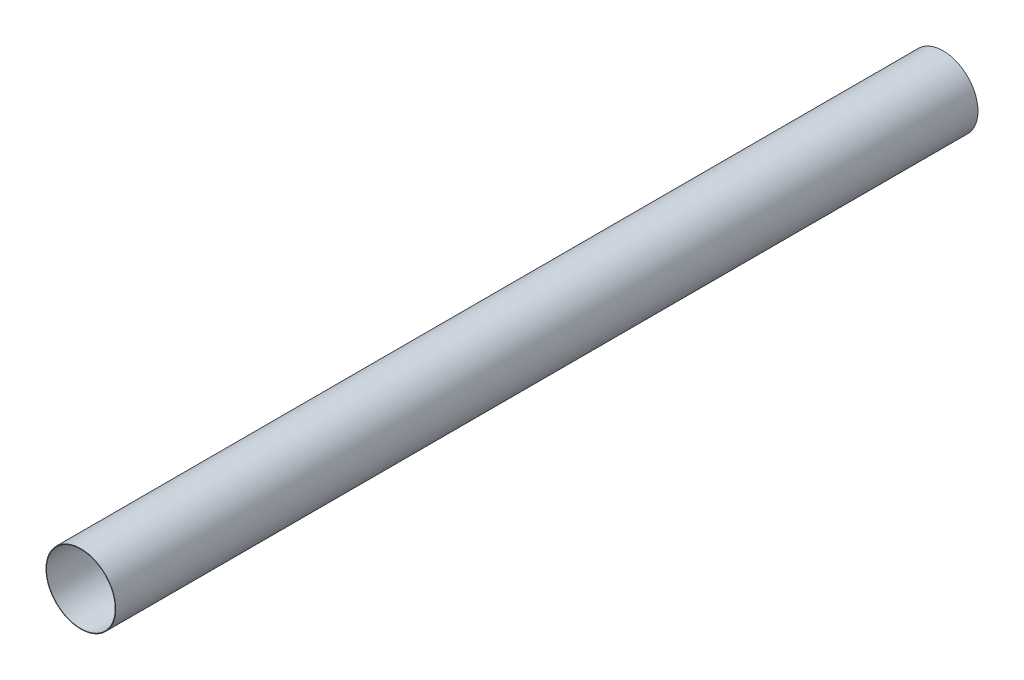
SolidWorks part; units mm, degrees
material "6061-T6 (SS)"
ref_plane "Front Plane" through (0, 0, 0) normal (0, 0, 1) x (1, 0, 0)
ref_plane "Top Plane" through (0, 0, 0) normal (0, 1, 0) x (1, 0, 0)
ref_plane "Right Plane" through (0, 0, 0) normal (1, 0, 0) x (0, 0, -1)
other "Center of Mass"
sketch "Sketch1" plane through (0, 0, 0) normal (0, 0, 1) x (1, 0, 0)
  circle A0 centre (0, 0) radius 72
  circle A1 centre (0, 0) radius 73
  dimension "D1" = 146
  dimension "D2" = 1
extrude "Boss-Extrude1" add sketch "Sketch1" along normal blind 1804
ref_plane "Mid-Plane" through (0, 0, 902) normal (0, 0, 1) x (1, 0, 0)
ref_axis "Axis1" through (0, 0, 1902.5) along (0, 0, -1)
ref_plane "Plane1" through (0, 0, 1834) normal (0, 0, 1) x (1, 0, 0)
